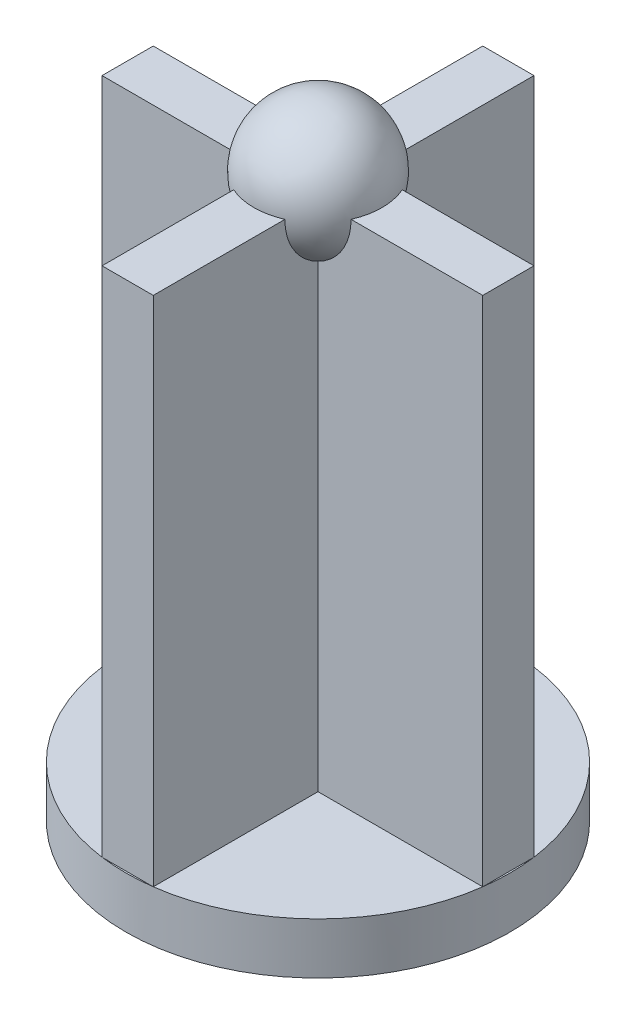
SolidWorks part; units mm, degrees
ref_plane "Front Plane" through (0, 0, 0) normal (0, 0, 1) x (1, 0, 0)
ref_plane "Top Plane" through (0, 0, 0) normal (0, 1, 0) x (1, 0, 0)
ref_plane "Right Plane" through (0, 0, 0) normal (1, 0, 0) x (0, 0, -1)
sketch "Sketch1" plane through (0, 0, 0) normal (0, 1, 0) x (1, 0, 0)
  circle A0 centre (0, 0) radius 37.5
  dimension "D1" = 75
extrude "Boss-Extrude1" add sketch "Sketch1" along normal blind 10
sketch "Sketch3" plane through (0, 10, 0) normal (0, 1, 0) x (1, 0, 0)
  line L0 (-5, 5) -> (-5, 37.1652)
  line L1 (-5.1863, 0) -> (5.6185, 0) construction
  line L2 (-5, 37.1652) -> (5, 37.1652)
  line L3 (5, 5) -> (5, 37.1652)
  line L4 (0, 5.624) -> (0, -4.7967) construction
  line L5 (5, 5) -> (37.1652, 5)
  line L6 (5, -5) -> (37.1652, -5)
  line L7 (37.1652, 5) -> (37.1652, -5)
  line L8 (-5.1863, 0) -> (5.6185, 0) construction
  line L9 (-5, -5) -> (-5, -37.1652)
  line L10 (5, -5) -> (5, -37.1652)
  line L11 (-5, -37.1652) -> (5, -37.1652)
  line L12 (0, 5.624) -> (0, -4.7967) construction
  line L13 (-5, 5) -> (-37.1652, 5)
  line L14 (-5, -5) -> (-37.1652, -5)
  line L15 (-37.1652, 5) -> (-37.1652, -5)
  line L16 (0, 37.1652) -> (0, 0) construction
  line L17 (0, 0) -> (37.1652, 0) construction
  line L18 (0, 0) -> (0, -37.1652) construction
  line L20 (-37.1652, 0) -> (0, 0) construction
  circle A2 centre (0, 0) radius 37.5 construction
  point P21 (0, 0)
  point P25 (0, 0)
  point P26 (0, 0)
  point P27 (0, 0)
  dimension "D1" = 10
extrude "Boss-Extrude2" add sketch "Sketch3" along normal blind 100
sketch "Sketch4" plane through (0, 110, 0) normal (0, 1, 0) x (1, 0, 0)
  line L0 (0, 12.5) -> (0, -12.5)
  arc A0 (0, -12.5) -> (0, 12.5) centre (0, 0) ccw
  dimension "D1" = 25
revolve "Revolve3" add sketch "Sketch4" angle 360 about L0
